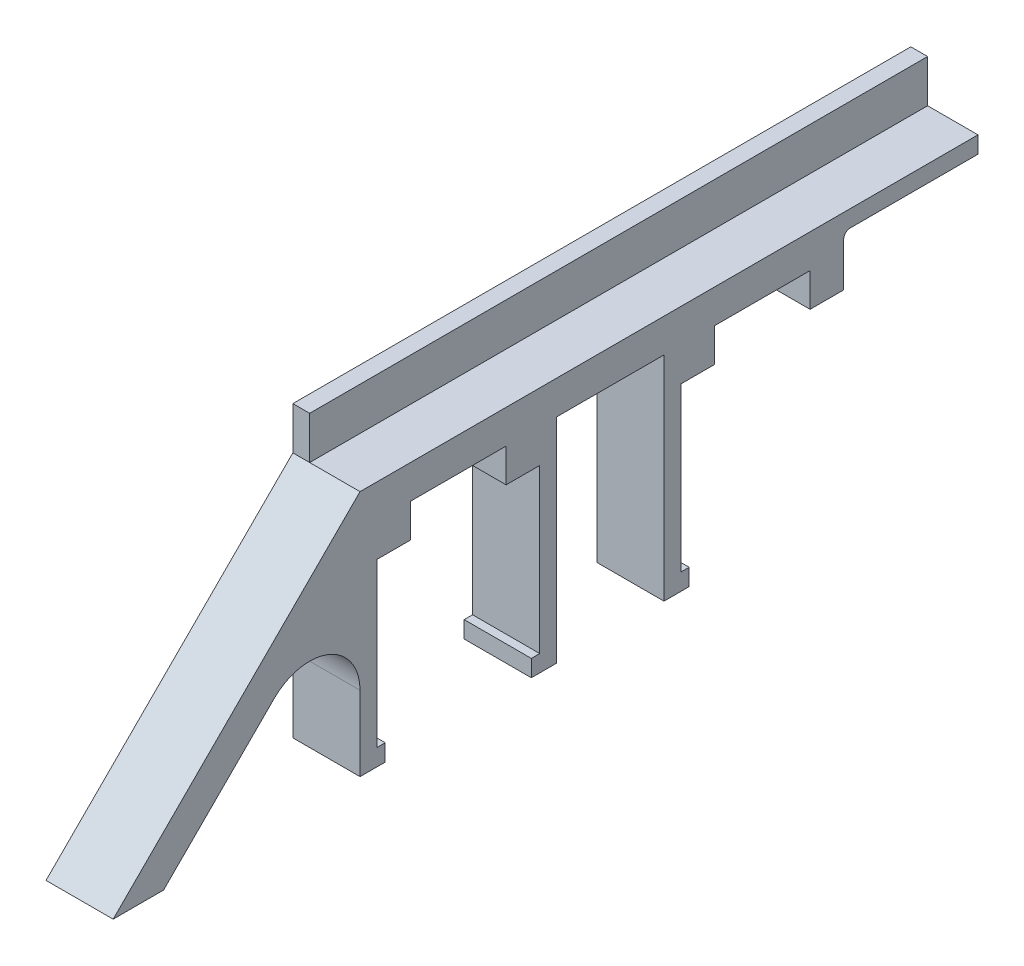
SolidWorks part; units mm, degrees
ref_plane "Front" through (0, 0, 0) normal (0, 0, 1) x (1, 0, 0)
ref_plane "Top" through (0, 0, 0) normal (0, 1, 0) x (1, 0, 0)
ref_plane "Right" through (0, 0, 0) normal (1, 0, 0) x (0, 0, -1)
sketch "Sketch1" plane through (0, 0, 0) normal (1, 0, 0) x (0, 0, -1)
  line L16 (-5, 68.5) -> (-5, -5)
  line L17 (-5, -5) -> (2.5, -5)
  line L18 (2.5, -5) -> (2.5, 0)
  line L19 (2.5, 0) -> (0, 0)
  line L20 (0, 0) -> (0, 48.5)
  line L21 (0, 48.5) -> (10, 48.5)
  line L22 (10, 48.5) -> (10, 58.5)
  line L23 (10, 58.5) -> (38.5, 58.5)
  line L24 (38.5, 58.5) -> (38.5, 48.5)
  line L25 (38.5, 48.5) -> (48.5, 48.5)
  line L26 (48.5, 48.5) -> (48.5, 0)
  line L27 (48.5, 0) -> (53.5, 0)
  line L28 (53.5, 0) -> (53.5, 58.5)
  line L29 (53.5, 58.5) -> (85.5, 58.5)
  line L30 (69.5, 58.5) -> (69.5, 90.1855)
  line L31 (-5, 68.5) -> (144, 68.5)
  line L32 (85.5, 0) -> (85.5, 58.5)
  line L33 (90.5, 0) -> (85.5, 0)
  line L34 (90.5, 48.5) -> (90.5, 0)
  line L35 (100.5, 48.5) -> (90.5, 48.5)
  line L36 (100.5, 58.5) -> (100.5, 48.5)
  line L37 (129, 58.5) -> (100.5, 58.5)
  line L38 (129, 48.5) -> (129, 58.5)
  line L39 (139, 48.5) -> (129, 48.5)
  line L40 (139, 0) -> (139, 48.5)
  line L41 (136.5, 0) -> (139, 0)
  line L42 (136.5, -5) -> (136.5, 0)
  line L43 (144, -5) -> (136.5, -5)
  line L44 (144, 68.5) -> (144, -5)
  line L45 (48.5, 0) -> (46, 0)
  line L46 (46, 0) -> (46, -5)
  line L47 (53.5, 0) -> (53.5, -5)
  line L48 (53.5, -5) -> (46, -5)
  line L49 (85.5, 0) -> (85.5, -5)
  line L50 (85.5, -5) -> (93, -5)
  line L51 (93, 0) -> (93, -5)
  line L52 (90.5, 0) -> (93, 0)
  line L53 (90.5, 0) -> (85.5, 0)
  line L54 (139, 48.5) -> (139, 68.5)
  line L55 (-5, 68.5) -> (-78.5, -5)
  line L56 (-5, -5) -> (-78.5, -5)
  line L57 (-78.5, -5) -> (-63.5, -5)
  line L58 (-63.5, -5) -> (-5, 53.5)
  line L59 (139, 63.5) -> (179, 63.5)
  line L60 (179, 63.5) -> (179, 68.5)
  line L61 (179, 68.5) -> (144, 68.5)
  point P9 (51, 0)
  point P32 (69.5, 68.5)
  dimension "D1" = 20
  dimension "D2" = 20
  dimension "D3" = 2.5
  dimension "D4" = 5
  dimension "D5" = 48.5
  dimension "D6" = 42
  dimension "D7" = 10
  dimension "D8" = 10
  dimension "D9" = 5
  dimension "D10" = 48.5
  dimension "D11" = 48.5
  dimension "D12" = 5
  dimension "D13" = 5
  dimension "D14" = 2.5
  dimension "D15" = 45
  dimension "D16" = 90
  dimension "D17" = 15
  dimension "D18" = 10
  dimension "D19" = 0
  dimension "D20" = 15
  dimension "D21" = 35
  dimension "D22" = 5
extrude "Boss-Extrude2" add sketch "Sketch1" along normal blind 20 contours L56 L58 L16 L55 | L31 L16 L17 L18 L19 L20 L21 L22 L23 L24 L25 L26 L27 L28 L29 L30 | L39 L54 L31 L30 L29 L32 L33 L34 L35 L36 L37 L38 | L52 L33 L49 L50 L51 | L48 L47 L27 L45 L46 | L44 L31 L54 | L60 L61 L44 region at (0, 67.4535, -32.25) region at (0, 28.142, 38.142) region at (0, 67.5242, -104.25) region at (0, 66, -141.5) region at (0, 66, -161.5) region at (0, -2.5, -49.75) region at (0, -2.5, -89.25)
fillet "Fillet1" radius 15 1 edges at (10, 53.5, 5)
fillet "Fillet2" radius 2 1 edges at (10, 63.5, -139)
sketch "Sketch2" plane through (0, 68.5, 0) normal (0, 1, 0) x (1, 0, 0)
  line L1 (5, 35) -> (5, 179)
  line L2 (20, 179) -> (0, 179) construction
  line L3 (0, -5) -> (0, 179) construction
  line L4 (20, -5) -> (0, -5) construction
  line L5 (0, -5) -> (0, 179)
  line L6 (0, 179) -> (5, 179)
  line L7 (5, 35) -> (5, -5)
  line L8 (5, -5) -> (0, -5)
  dimension "D1" = 5
  dimension "D2" = 40
extrude "Boss-Extrude3" add sketch "Sketch2" along normal blind 12.7
